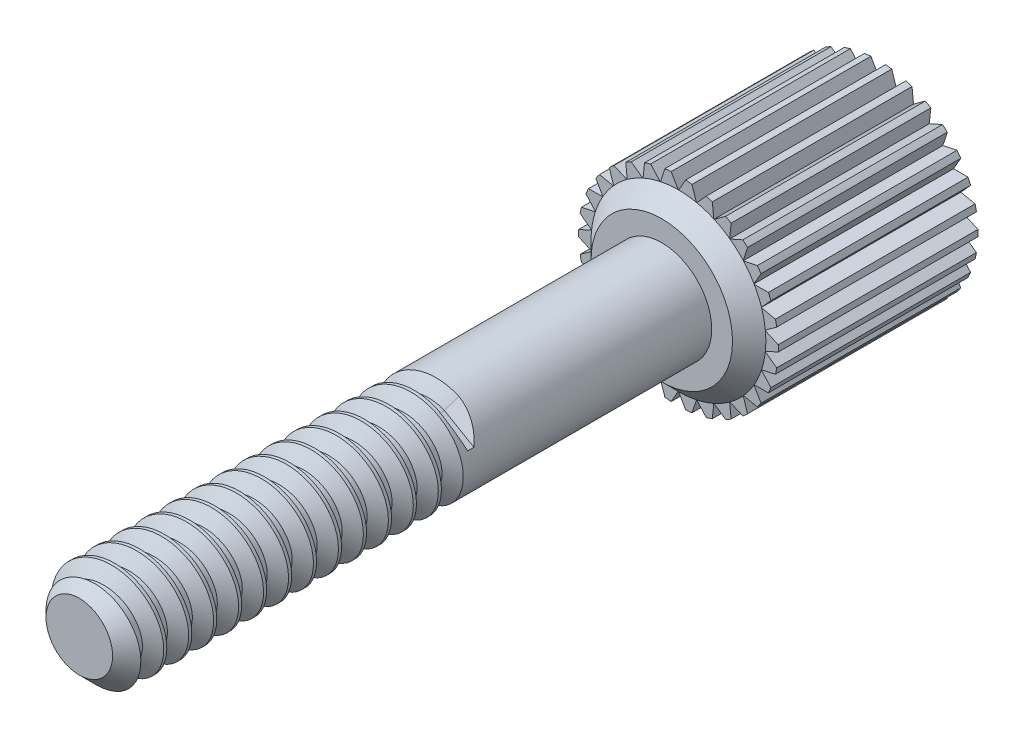
SolidWorks part; units mm, degrees
ref_plane "Спереди" through (0, 0, 0) normal (0, 0, 1) x (1, 0, 0)
ref_plane "Сверху" through (0, 0, 0) normal (0, 1, 0) x (1, 0, 0)
ref_plane "Справа" through (0, 0, 0) normal (1, 0, 0) x (0, 0, -1)
sketch "Эскиз1" plane through (0, 0, 0) normal (0, 0, 1) x (1, 0, 0)
  circle A0 centre (0, 0) radius 6
  dimension "D1" = 12
extrude "Бобышка-Вытянуть1" add sketch "Эскиз1" along normal blind 12
sketch "Эскиз2" plane through (0, 0, 12) normal (0, 0, 1) x (1, 0, 0)
  line L0 (-0.5, 6.0941) -> (0, 5.2281)
  line L1 (0, 5.2281) -> (0.5, 6.0941)
  line L2 (0.5, 6.0941) -> (-0.5, 6.0941)
  point P2 (0, 0)
  dimension "D1" = 1
  dimension "D2" = 1
  dimension "D3" = 1
extrude "Вырез-Вытянуть1" cut sketch "Эскиз2" against normal blind 12
pattern_circular "Круговой массив1" count 30 over 360 about axis through (0, 0, 12) along (0, 0, 1) of "Вырез-Вытянуть1"
sketch "Эскиз3" plane through (0, 0, 12) normal (0, 0, 1) x (1, 0, 0)
  circle A0 centre (0, 0) radius 5.25
  dimension "D1" = 10.5
extrude "Бобышка-Вытянуть3" add sketch "Эскиз3" along normal blind 1
chamfer "Фаска1" distance 1 angle 45 1 edges at (5.25, 0, 13)
sketch "Эскиз4" plane through (0, 0, 13) normal (0, 0, 1) x (1, 0, 0)
  circle A0 centre (0, 0) radius 3
  dimension "D1" = 6
extrude "Бобышка-Вытянуть4" add sketch "Эскиз4" along normal blind 35
chamfer "Фаска2" distance 1 angle 45 1 edges at (3, 0, 48)
thread "Резьба1" pitch 1.5 method cut profile "Профиль резьбы1" start angle 0, offset 1, length 20, pitch 1.5, diameter 6
ref_plane "Плоскость1" through (-3, 0, 48) normal (0, -1, 0) x (-1, 0, 0)
sketch "Профиль резьбы1" plane through (-3, 0, 48) normal (0, -1, 0) x (-1, 0, 0)
  line L0 (0, 0) -> (0, 1.5) construction
  line L11 (0, 0) -> (0, 1.3125)
  line L12 (0, 1.3125) -> (-0.8119, 0.8437)
  line L13 (-0.8119, 0.8437) -> (-0.8119, 0.4687)
  line L15 (-0.8119, 0.4687) -> (0, 0)
  line L17 (-0.8119, 0.6562) -> (0, 0.6562) construction
  point P2 (0, 0)
  dimension "Pitch" = 1.5
  dimension "Profile_Angle" = 60
  dimension "Profile_Land" = 0.375
  dimension "Profile_Height" = 0.8119
sketch "Эскиз11" plane through (0.0005, -0.0003, 0) normal (-0.866, 0.5, 0) x (0.5, 0.866, 0.0001)
  line L4 (2.1905, -27.5303) -> (3.0024, -27.999)
  line L5 (3.0024, -27.999) -> (3.0023, -26.6865)
  line L6 (3.0023, -26.6865) -> (2.1904, -27.1553)
  line L7 (2.1904, -27.1553) -> (2.1905, -27.5303)
  line L8 (2.1905, -27.5303) -> (3.0024, -27.999)
  line L9 (3.0024, -27.999) -> (3.0023, -26.6865)
  line L10 (3.0023, -26.6865) -> (2.1904, -27.1553)
  line L11 (2.1904, -27.1553) -> (2.1905, -27.5303)
  dimension "D1" = 0
extrude "Вырез-Вытянуть2" cut sketch "Эскиз11" against normal blind 30
sketch "Эскиз12" plane through (0, 0, 0) normal (0, 1, 0) x (1, 0, 0)
  line L4 (-3, -47) -> (-2.366, -47.634)
  line L5 (-2.1881, -47.5313) -> (-2.1881, -47.1563)
  line L6 (-2.1881, -47.1563) -> (-3, -46.6875)
  line L7 (-3, -46.6875) -> (-3, -47)
  line L9 (-2.1881, -47.5313) -> (-2.1881, -47.1563)
  line L10 (-2.1881, -47.1563) -> (-3, -46.6875)
  line L11 (-3, -46.6875) -> (-3, -47)
  line L13 (-3, -47) -> (-2.366, -47.634)
  line L14 (-2.366, -47.634) -> (-2.1881, -47.5313)
  line L15 (-2.366, -47.634) -> (-2.1881, -47.5313)
  dimension "D1" = 0
extrude "Вырез-Вытянуть3" cut sketch "Эскиз12" against normal blind 30
